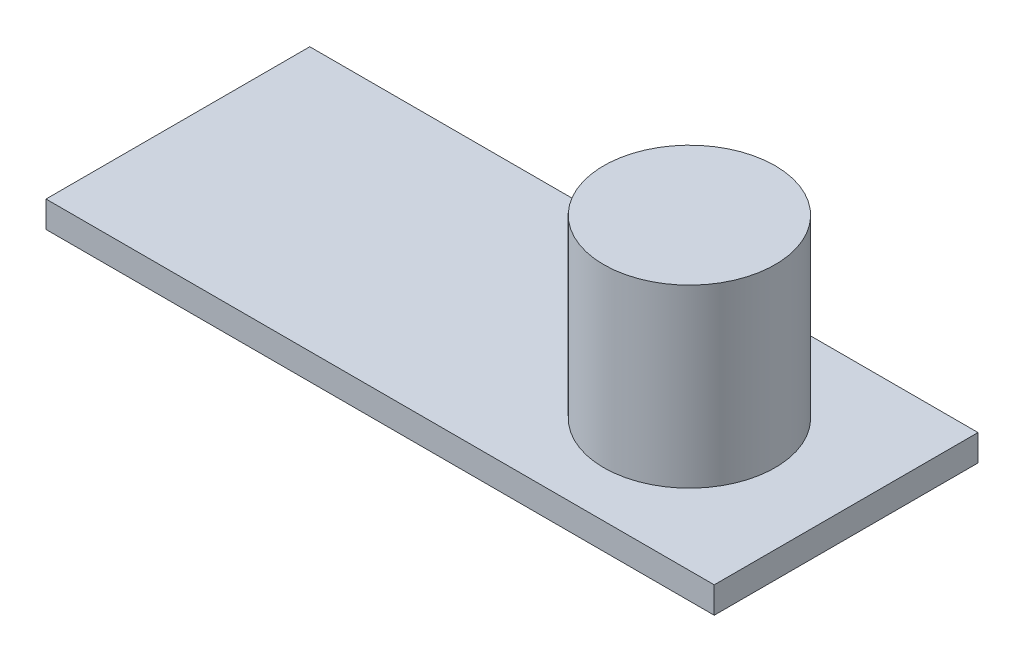
SolidWorks part; units mm, degrees
ref_plane "Front Plane" through (0, 0, 0) normal (0, 0, 1) x (1, 0, 0)
ref_plane "Top Plane" through (0, 0, 0) normal (0, 1, 0) x (1, 0, 0)
ref_plane "Right Plane" through (0, 0, 0) normal (1, 0, 0) x (0, 0, -1)
sketch "Sketch1" plane through (0, 0, 0) normal (0, 1, 0) x (1, 0, 0)
  line L1 (19, 7.5) -> (-19, 7.5)
  line L2 (19, 7.5) -> (19, -7.5)
  line L3 (19, -7.5) -> (-19, -7.5)
  line L4 (-19, 7.5) -> (-19, -7.5)
  line L5 (19, 7.5) -> (-19, -7.5) construction
  line L6 (19, -7.5) -> (-19, 7.5) construction
  circle A0 centre (10.09, 0) radius 4.875
  point P0 (0, 0)
  dimension "D5" = 9.75
  dimension "D1" = 38
  dimension "D2" = 15
  dimension "D3" = 7.5
  dimension "D4" = 29.09
extrude "Boss-Extrude1" add sketch "Sketch1" against normal blind 1.5 contours A0 | L1 L4 L3 L2 A0 | A0 | L2 L1 L4 L3 region at (-1.5209, 0, 0) region at (10.09, 0, 0)
extrude "Boss-Extrude2" add sketch "Sketch1<3>" along normal blind 10 contours A0 region at (10.09, 0, 0)
sketch "Sketch1<3>" plane through (0, 0, 0) normal (0, 1, 0) x (1, 0, 0) same geometry as "Sketch1"
